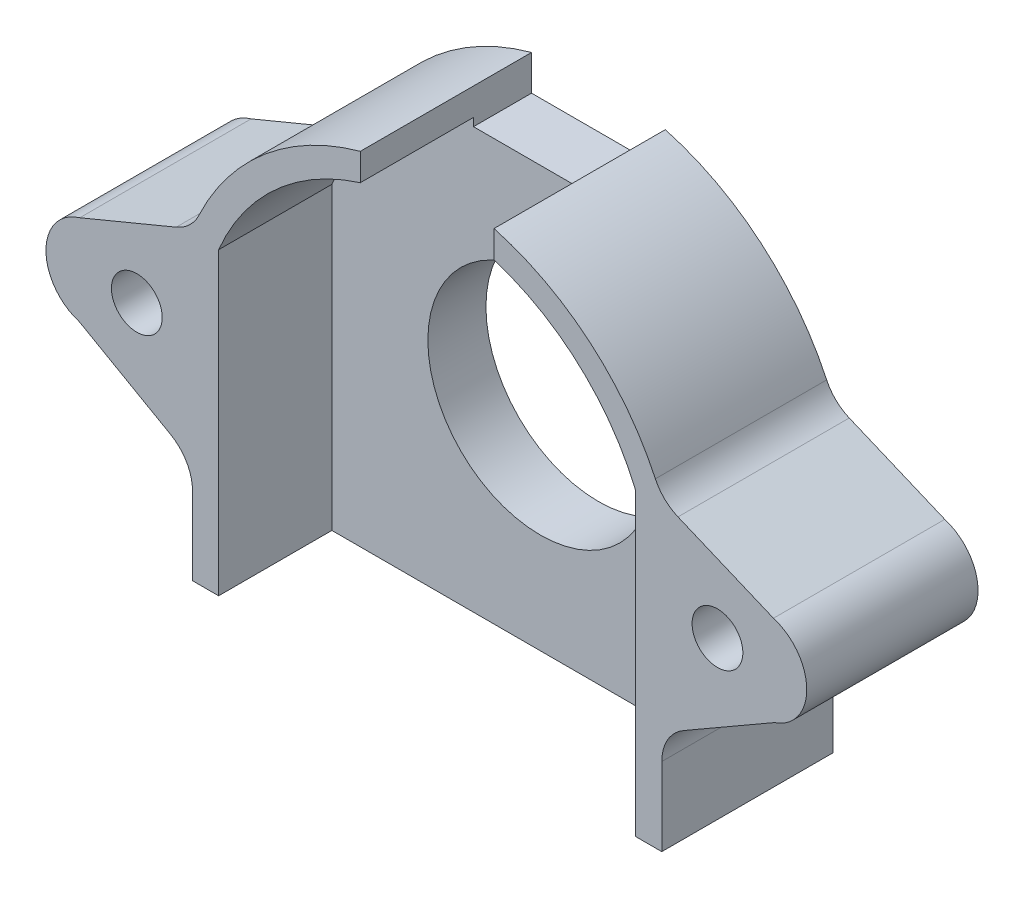
SolidWorks part; units mm, degrees
ref_plane "Front Plane" through (0, 0, 0) normal (0, 0, 1) x (1, 0, 0)
ref_plane "Top Plane" through (0, 0, 0) normal (0, 1, 0) x (1, 0, 0)
ref_plane "Right Plane" through (0, 0, 0) normal (1, 0, 0) x (0, 0, -1)
ref_axis "X-Axis" through (-88.99, 0, 0) along (1, 0, 0)
ref_axis "Y-Axis" through (0, 55, 0) along (0, -1, 0)
ref_axis "Z-Axis" through (0, 0, 55) along (0, 0, -1)
sketch "Sketch1" plane through (0, 0, 0) normal (0, 0, 1) x (1, 0, 0)
  line L0 (-8.5276, -16.5266) -> (-13.5659, -12.73)
  line L1 (13.5631, -12.73) -> (8.4672, -16.57)
  line L2 (7, -15.5076) -> (7, -17.4114)
  line L3 (-7.0071, -15.5076) -> (-7.0071, -17.404)
  line L12 (4.0612, 14.3117) -> (-4.0612, 14.3117)
  line L13 (14.1639, -12.6559) -> (14.1639, 5.9526)
  line L15 (8.4672, -17.4114) -> (8.4672, -16.57)
  line L16 (7, -17.4114) -> (8.4672, -17.4114)
  line L19 (7, -15.5076) -> (-7.0071, -15.5076)
  line L22 (-8.5276, -17.404) -> (-7.0071, -17.404)
  line L23 (-14.1639, 5.9526) -> (-14.1639, -12.6477)
  line L24 (-4.0612, 14.3117) -> (-4.6066, 14.657)
  line L25 (4.6066, 14.657) -> (4.0612, 14.3117)
  line L26 (-8.5276, -17.404) -> (-8.5276, -16.5266)
  line L29 (-13.5659, -12.73) -> (-14.1639, -12.6477)
  line L30 (14.1639, -12.6559) -> (13.5631, -12.73)
  line L32 (-88.99, 0) -> (88.99, 0) construction
  line L33 (0, 55) -> (0, -55) construction
  arc A2 (14.1639, 5.9526) -> (4.6066, 14.657) centre (0, 0) ccw
  arc A3 (-4.6066, 14.657) -> (-14.1639, 5.9526) centre (0, 0) ccw
  dimension "D5" = 15.3639
  dimension "D6" = 15.3639
  dimension "D1" = 15.5076
  dimension "D2" = 14.1639
  dimension "D3" = 14.1639
  dimension "D4" = 14.3117
  dimension "D7" = 5.9526
  dimension "D8" = 8.7044
  dimension "D9" = 9.5572
  dimension "D10" = 147.663
  dimension "D11" = 4.6066
  dimension "D12" = 147.663
  dimension "D13" = 1.9039
  dimension "D14" = 7
  dimension "D15" = 7.0071
  dimension "D16" = 143
  dimension "D17" = 8.5276
  dimension "D18" = 8.4672
  dimension "D19" = 143
  dimension "D20" = 5.0959
  dimension "D21" = 209.169
  dimension "D22" = 5.0383
  dimension "D23" = 12.73
  dimension "D24" = 209.969
  dimension "D25" = 1.8964
sketch "Sketch2" plane through (0, 0, 0) normal (0, 0, 1) x (1, 0, 0)
  line L48 (3.4813, 16.3117) -> (-3.4813, 16.3117)
  line L49 (-3.4813, 16.3117) -> (-4.2922, 16.825)
  line L50 (-16.1639, 6.343) -> (-16.1639, -14.3915)
  line L51 (-16.1639, -14.3915) -> (-14.3539, -14.6404)
  line L52 (-14.3539, -14.6404) -> (-10.5276, -17.5238)
  line L53 (-10.5276, -17.5238) -> (-10.5276, -19.404)
  line L54 (-10.5276, -19.404) -> (-5.0071, -19.404)
  line L55 (-5.0071, -19.404) -> (-5.0071, -17.5076)
  line L56 (-5.0071, -17.5076) -> (5, -17.5076)
  line L57 (5, -17.5076) -> (5, -19.4114)
  line L58 (5, -19.4114) -> (10.4672, -19.4114)
  line L59 (10.4672, -19.4114) -> (10.4672, -17.5672)
  line L60 (10.4672, -17.5672) -> (14.3392, -14.6494)
  line L61 (14.3392, -14.6494) -> (16.1639, -14.4244)
  line L62 (16.1639, -14.4244) -> (16.1639, 6.343)
  line L63 (4.2922, 16.825) -> (3.4813, 16.3117)
  line L64 (3.4813, 16.3117) -> (-3.4813, 16.3117)
  line L65 (-3.4813, 16.3117) -> (-4.2922, 16.825)
  line L66 (-16.1639, 6.343) -> (-16.1639, -14.3915)
  line L67 (-16.1639, -14.3915) -> (-14.3539, -14.6404)
  line L68 (-14.3539, -14.6404) -> (-10.5276, -17.5238)
  line L69 (-10.5276, -17.5238) -> (-10.5276, -19.404)
  line L70 (-10.5276, -19.404) -> (-5.0071, -19.404)
  line L71 (-5.0071, -19.404) -> (-5.0071, -17.5076)
  line L72 (-5.0071, -17.5076) -> (5, -17.5076)
  line L73 (5, -17.5076) -> (5, -19.4114)
  line L74 (5, -19.4114) -> (10.4672, -19.4114)
  line L75 (10.4672, -19.4114) -> (10.4672, -17.5672)
  line L76 (10.4672, -17.5672) -> (14.3392, -14.6494)
  line L77 (14.3392, -14.6494) -> (16.1639, -14.4244)
  line L78 (16.1639, -14.4244) -> (16.1639, 6.343)
  line L79 (4.2922, 16.825) -> (3.4813, 16.3117)
  arc A6 (-4.2922, 16.825) -> (-16.1639, 6.343) centre (0, 0) ccw
  arc A7 (16.1639, 6.343) -> (4.2922, 16.825) centre (0, 0) ccw
  arc A8 (-4.2922, 16.825) -> (-16.1639, 6.343) centre (0, 0) ccw
  arc A9 (16.1639, 6.343) -> (4.2922, 16.825) centre (0, 0) ccw
  dimension "D1" = 2
extrude "Boss-Extrude1" add sketch "Sketch2" along normal blind 4
sketch "Sketch3" plane through (0, 0, 4) normal (0, 0, 1) x (1, 0, 0)
  line L16 (4.2922, 16.825) -> (3.4813, 16.3117)
  line L17 (3.4813, 16.3117) -> (-3.4813, 16.3117)
  line L18 (-3.4813, 16.3117) -> (-4.2922, 16.825)
  line L19 (-16.1639, 6.343) -> (-16.1639, -14.3915)
  line L20 (-16.1639, -14.3915) -> (-14.3539, -14.6404)
  line L21 (-14.3539, -14.6404) -> (-10.5276, -17.5238)
  line L22 (-10.5276, -17.5238) -> (-10.5276, -19.404)
  line L23 (-10.5276, -19.404) -> (-5.0071, -19.404)
  line L24 (-5.0071, -19.404) -> (-5.0071, -17.5076)
  line L25 (-5.0071, -17.5076) -> (5, -17.5076)
  line L26 (5, -17.5076) -> (5, -19.4114)
  line L27 (5, -19.4114) -> (10.4672, -19.4114)
  line L28 (10.4672, -19.4114) -> (10.4672, -17.5672)
  line L29 (10.4672, -17.5672) -> (14.3392, -14.6494)
  line L30 (14.3392, -14.6494) -> (16.1639, -14.4244)
  line L31 (16.1639, -14.4244) -> (16.1639, 6.343)
  line L32 (4.2922, 16.825) -> (3.4813, 16.3117)
  line L33 (3.4813, 16.3117) -> (-3.4813, 16.3117)
  line L34 (-3.4813, 16.3117) -> (-4.2922, 16.825)
  line L35 (-16.1639, 6.343) -> (-16.1639, -14.3915)
  line L36 (-16.1639, -14.3915) -> (-14.3539, -14.6404)
  line L37 (-14.3539, -14.6404) -> (-10.5276, -17.5238)
  line L38 (-10.5276, -17.5238) -> (-10.5276, -19.404)
  line L39 (-10.5276, -19.404) -> (-5.0071, -19.404)
  line L40 (-5.0071, -19.404) -> (-5.0071, -17.5076)
  line L41 (-5.0071, -17.5076) -> (5, -17.5076)
  line L42 (5, -17.5076) -> (5, -19.4114)
  line L43 (5, -19.4114) -> (10.4672, -19.4114)
  line L44 (10.4672, -19.4114) -> (10.4672, -17.5672)
  line L45 (10.4672, -17.5672) -> (14.3392, -14.6494)
  line L46 (14.3392, -14.6494) -> (16.1639, -14.4244)
  line L47 (16.1639, -14.4244) -> (16.1639, 6.343)
  line L64 (4.0032, 14.5117) -> (-4.0032, 14.5117)
  line L65 (-4.0032, 14.5117) -> (-4.5778, 14.8754)
  line L66 (-14.3639, 5.9928) -> (-14.3639, -12.8221)
  line L67 (-14.3639, -12.8221) -> (-13.6447, -12.921)
  line L68 (-13.6447, -12.921) -> (-8.7276, -16.6263)
  line L69 (-8.7276, -16.6263) -> (-8.7276, -17.604)
  line L70 (-8.7276, -17.604) -> (-6.8071, -17.604)
  line L71 (-6.8071, -17.604) -> (-6.8071, -15.7076)
  line L72 (-6.8071, -15.7076) -> (6.8, -15.7076)
  line L73 (6.8, -15.7076) -> (6.8, -17.6114)
  line L74 (6.8, -17.6114) -> (8.6672, -17.6114)
  line L75 (8.6672, -17.6114) -> (8.6672, -16.6697)
  line L76 (8.6672, -16.6697) -> (13.6407, -12.9219)
  line L77 (13.6407, -12.9219) -> (14.3639, -12.8328)
  line L78 (14.3639, -12.8328) -> (14.3639, 5.9928)
  line L79 (4.5778, 14.8754) -> (4.0032, 14.5117)
  line L80 (4.0032, 14.5117) -> (-4.0032, 14.5117)
  line L81 (-4.0032, 14.5117) -> (-4.5778, 14.8754)
  line L82 (-14.3639, 5.9928) -> (-14.3639, -12.8221)
  line L83 (-14.3639, -12.8221) -> (-13.6447, -12.921)
  line L84 (-13.6447, -12.921) -> (-8.7276, -16.6263)
  line L85 (-8.7276, -16.6263) -> (-8.7276, -17.604)
  line L86 (-8.7276, -17.604) -> (-6.8071, -17.604)
  line L87 (-6.8071, -17.604) -> (-6.8071, -15.7076)
  line L88 (-6.8071, -15.7076) -> (6.8, -15.7076)
  line L89 (6.8, -15.7076) -> (6.8, -17.6114)
  line L90 (6.8, -17.6114) -> (8.6672, -17.6114)
  line L91 (8.6672, -17.6114) -> (8.6672, -16.6697)
  line L92 (8.6672, -16.6697) -> (13.6407, -12.9219)
  line L93 (13.6407, -12.9219) -> (14.3639, -12.8328)
  line L94 (14.3639, -12.8328) -> (14.3639, 5.9928)
  line L95 (4.5778, 14.8754) -> (4.0032, 14.5117)
  arc A2 (-4.2922, 16.825) -> (-16.1639, 6.343) centre (0, 0) ccw
  arc A3 (16.1639, 6.343) -> (4.2922, 16.825) centre (0, 0) ccw
  arc A4 (-4.2922, 16.825) -> (-16.1639, 6.343) centre (0, 0) ccw
  arc A5 (16.1639, 6.343) -> (4.2922, 16.825) centre (0, 0) ccw
  arc A8 (-4.5778, 14.8754) -> (-14.3639, 5.9928) centre (0, 0) ccw
  arc A9 (14.3639, 5.9928) -> (4.5778, 14.8754) centre (0, 0) ccw
  arc A10 (-4.5778, 14.8754) -> (-14.3639, 5.9928) centre (0, 0) ccw
  arc A11 (14.3639, 5.9928) -> (4.5778, 14.8754) centre (0, 0) ccw
  dimension "D1" = 0
  dimension "D2" = 0.2
extrude "Boss-Extrude2" add sketch "Sketch3" along normal blind 7.8
sketch "Sketch4" plane through (0, 0, 0) normal (0, 0, -1) x (-1, 0, 0)
  line L0 (-4.6066, 14.657) -> (-4.6066, 16.7416)
  line L2 (-4.6066, 14.657) -> (-4.6066, 14.3117)
  line L4 (-4.6066, 14.3117) -> (4.6066, 14.3117)
  line L5 (4.6066, 14.3117) -> (4.6066, 14.657)
  line L6 (4.6066, 14.657) -> (4.6066, 16.7416)
  line L26 (-16.1639, -14.4244) -> (-16.1639, 6.343) construction
  line L27 (-16.1639, -12.6559) -> (17.6174, -12.6559)
  line L28 (-16.1639, -12.6559) -> (-16.1639, -23.4664)
  line L29 (-16.1639, -23.4664) -> (17.6174, -23.4664)
  line L30 (17.6174, -12.6559) -> (17.6174, -23.4664)
  line L31 (4.6066, 16.7416) -> (2.7216, 20.6711)
  line L32 (2.7216, 20.6711) -> (-2.4857, 20.4886)
  line L33 (-2.4857, 20.4886) -> (-4.6066, 16.7416)
  arc A0 (-4.2922, 16.825) -> (-16.1639, 6.343) centre (0, 0) ccw construction
  arc A1 (16.1639, 6.343) -> (4.2922, 16.825) centre (0, 0) ccw construction
extrude "Cut-Extrude1" cut sketch "Sketch4" against normal through all
sketch "Sketch6" plane through (0, 0, 11.8) normal (0, 0, 1) x (1, 0, 0)
  line L17 (-16.1639, -7.5427) -> (-16.1639, 6.343)
  line L18 (16.1639, -7.5427) -> (16.1639, 6.343)
  line L19 (16.1639, -12.6559) -> (16.1639, 6.343) construction
  line L34 (23.8592, 3.1178) -> (16.1639, 6.343)
  line L35 (16.1639, -7.5427) -> (23.9259, -3.0727)
  line L49 (-23.9485, -3.1122) -> (-16.1639, -7.5427)
  line L50 (-16.1639, 6.343) -> (-23.9298, 3.1178)
  circle A2 centre (-20, 0) radius 1.75
  circle A4 centre (20, 0) radius 1.75
  arc A10 (23.9259, -3.0727) -> (23.8592, 3.1178) centre (22.9022, 0.0119) ccw
  arc A11 (-23.9298, 3.1178) -> (-23.9485, -3.1122) centre (-23.0122, 0) ccw
  dimension "D2" = 3.5
  dimension "D4" = 3.5
  dimension "D1" = 20
  dimension "D3" = 20
extrude "Boss-Extrude3" add sketch "Sketch6" against normal blind 3
fillet "Fillet1" radius 3 4 edges at (-16.1639, 6.343, 10.3) (-16.1639, -7.5427, 10.3) (16.1639, -7.5427, 10.3) (16.1639, 6.343, 10.3)
sketch "Sketch7" plane through (0, 0, 0) normal (0, 0, -1) x (-1, 0, 0)
  line L17 (-15.6829, 7.6555) -> (-24.0176, 3.1178)
  line L18 (-24.0363, -3.1122) -> (-16.2516, -7.5427)
  line L19 (-16.2516, -7.5427) -> (-16.2516, -14.7567)
  line L20 (-16.2516, -14.7567) -> (-9.4382, -14.7567)
  line L21 (-16.2516, -14.7567) -> (-9.4382, -14.7567)
  line L22 (-9.4382, -14.7567) -> (-8.704, -15.3137)
  line L23 (-8.704, -15.3137) -> (-8.704, -17.5178)
  line L24 (-8.704, -17.5178) -> (-9.6393, -19.722)
  line L25 (-9.6393, -19.722) -> (9.6393, -19.722)
  line L26 (9.6393, -19.722) -> (8.704, -17.5178)
  line L27 (8.704, -17.5178) -> (8.704, -15.3137)
  line L28 (8.704, -15.3137) -> (9.4382, -14.7567)
  line L29 (9.4382, -14.7567) -> (16.2516, -14.7567)
  line L30 (9.4382, -14.7567) -> (16.2516, -14.7567)
  line L31 (16.2516, -14.7567) -> (16.2516, -7.5427)
  line L32 (16.2516, -7.5427) -> (24.0363, -3.1122)
  line L33 (24.0176, 3.1178) -> (15.6829, 7.6555)
  line L34 (-15.6829, 7.6555) -> (-24.0176, 3.1178)
  line L35 (-24.0363, -3.1122) -> (-16.2516, -7.5427)
  line L36 (-16.2516, -7.5427) -> (-16.2516, -14.7567)
  line L39 (-9.4382, -14.7567) -> (-8.704, -15.3137)
  line L40 (-8.704, -15.3137) -> (-8.704, -17.5178)
  line L41 (-8.704, -17.5178) -> (-9.6393, -19.722)
  line L42 (-9.6393, -19.722) -> (9.6393, -19.722)
  line L43 (9.6393, -19.722) -> (8.704, -17.5178)
  line L44 (8.704, -17.5178) -> (8.704, -15.3137)
  line L45 (8.704, -15.3137) -> (9.4382, -14.7567)
  line L48 (16.2516, -14.7567) -> (16.2516, -7.5427)
  line L49 (16.2516, -7.5427) -> (24.0363, -3.1122)
  line L50 (24.0176, 3.1178) -> (15.6829, 7.6555)
  circle A2 centre (0, 0) radius 7.75
  circle A3 centre (20, 0) radius 1.75
  circle A4 centre (20, 0) radius 1.75
  circle A5 centre (-20, 0) radius 1.75
  circle A6 centre (-20, 0) radius 1.75
  arc A9 (-24.0176, 3.1178) -> (-24.0363, -3.1122) centre (-23.1, 0) ccw
  arc A10 (24.0363, -3.1122) -> (24.0176, 3.1178) centre (23.1, 0) ccw
  arc A11 (15.6829, 7.6555) -> (-15.6829, 7.6555) centre (0, 0) ccw
  arc A12 (-24.0176, 3.1178) -> (-24.0363, -3.1122) centre (-23.1, 0) ccw
  arc A13 (24.0363, -3.1122) -> (24.0176, 3.1178) centre (23.1, 0) ccw
  arc A14 (15.6829, 7.6555) -> (-15.6829, 7.6555) centre (0, 0) ccw
  dimension "D1" = 15.5
  dimension "D2" = 0
  dimension "D3" = 0
  dimension "D4" = 0
extrude "Cut-Extrude2" cut sketch "Sketch7" against normal up to next contours A2
sketch "Sketch8" plane through (0, 0, 8.8) normal (0, 0, -1) x (-1, 0, 0)
  line L3 (-17.2794, 5.8754) -> (-23.8592, 3.1178)
  line L4 (-23.9259, -3.0727) -> (-17.6667, -6.6772)
  line L5 (-16.1639, -9.277) -> (-16.1639, 6.343)
  line L6 (-17.2794, 5.8754) -> (-23.8592, 3.1178)
  line L7 (-23.9259, -3.0727) -> (-17.6667, -6.6772)
  line L8 (-16.1639, -9.277) -> (-16.1639, 6.343)
  line L9 (17.6799, -6.6798) -> (23.9485, -3.1122)
  line L10 (23.9298, 3.1178) -> (17.2859, 5.877)
  line L11 (16.1639, 6.343) -> (16.1639, -9.2871)
  line L12 (17.6799, -6.6798) -> (23.9485, -3.1122)
  line L13 (23.9298, 3.1178) -> (17.2859, 5.877)
  line L14 (16.1639, 6.343) -> (16.1639, -9.2871)
  circle A0 centre (20, 0) radius 1.75 construction
  circle A1 centre (-20, 0) radius 1.75 construction
  circle A2 centre (20, 0) radius 1.75
  circle A3 centre (-20, 0) radius 1.75
  arc A4 (-23.8592, 3.1178) -> (-23.9259, -3.0727) centre (-22.9022, 0.0119) ccw
  arc A5 (-16.1639, -9.277) -> (-17.6667, -6.6772) centre (-19.1639, -9.277) ccw
  arc A6 (-15.7226, 7.3691) -> (-16.1639, 6.343) centre (0, 0) ccw
  arc A7 (-17.2794, 5.8754) -> (-15.7226, 7.3691) centre (-18.439, 8.6422) ccw
  arc A8 (-23.8592, 3.1178) -> (-23.9259, -3.0727) centre (-22.9022, 0.0119) ccw
  arc A9 (-16.1639, -9.277) -> (-17.6667, -6.6772) centre (-19.1639, -9.277) ccw
  arc A10 (-15.7226, 7.3691) -> (-16.1639, 6.343) centre (0, 0) ccw
  arc A11 (-17.2794, 5.8754) -> (-15.7226, 7.3691) centre (-18.439, 8.6422) ccw
  arc A12 (23.9485, -3.1122) -> (23.9298, 3.1178) centre (23.0122, 0) ccw
  arc A13 (15.7205, 7.3736) -> (17.2859, 5.877) centre (18.4366, 8.6475) ccw
  arc A14 (16.1639, 6.343) -> (15.7205, 7.3736) centre (0, 0) ccw
  arc A15 (17.6799, -6.6798) -> (16.1639, -9.2871) centre (19.1639, -9.2871) ccw
  arc A16 (23.9485, -3.1122) -> (23.9298, 3.1178) centre (23.0122, 0) ccw
  arc A17 (15.7205, 7.3736) -> (17.2859, 5.877) centre (18.4366, 8.6475) ccw
  arc A18 (16.1639, 6.343) -> (15.7205, 7.3736) centre (0, 0) ccw
  arc A19 (17.6799, -6.6798) -> (16.1639, -9.2871) centre (19.1639, -9.2871) ccw
  dimension "D1" = 0
  dimension "D2" = 0
extrude "Boss-Extrude4" add sketch "Sketch8" along normal up to surface (8.8 mm away) up to face at (-7.75, 0, 0)
sketch "Sketch9" plane through (0, -12.6559, 0) normal (0, -1, 0) x (1, 0, 0)
  line L8 (-16.1639, 0) -> (16.1639, 0)
  line L9 (16.1639, 0) -> (16.1639, 11.8)
  line L10 (16.1639, 11.8) -> (14.3639, 11.8)
  line L11 (14.3639, 11.8) -> (14.3639, 4)
  line L12 (14.3639, 4) -> (-14.3639, 4)
  line L13 (-14.3639, 4) -> (-14.3639, 11.8)
  line L14 (-14.3639, 11.8) -> (-16.1639, 11.8)
  line L15 (-16.1639, 11.8) -> (-16.1639, 0)
  line L16 (-16.1639, 0) -> (16.1639, 0)
  line L17 (16.1639, 0) -> (16.1639, 11.8)
  line L18 (16.1639, 11.8) -> (14.3639, 11.8)
  line L19 (14.3639, 11.8) -> (14.3639, 4)
  line L20 (14.3639, 4) -> (-14.3639, 4)
  line L21 (-14.3639, 4) -> (-14.3639, 11.8)
  line L22 (-14.3639, 11.8) -> (-16.1639, 11.8)
  line L23 (-16.1639, 11.8) -> (-16.1639, 0)
  dimension "D1" = 0
extrude "Boss-Extrude5" add sketch "Sketch9" along normal blind 2
